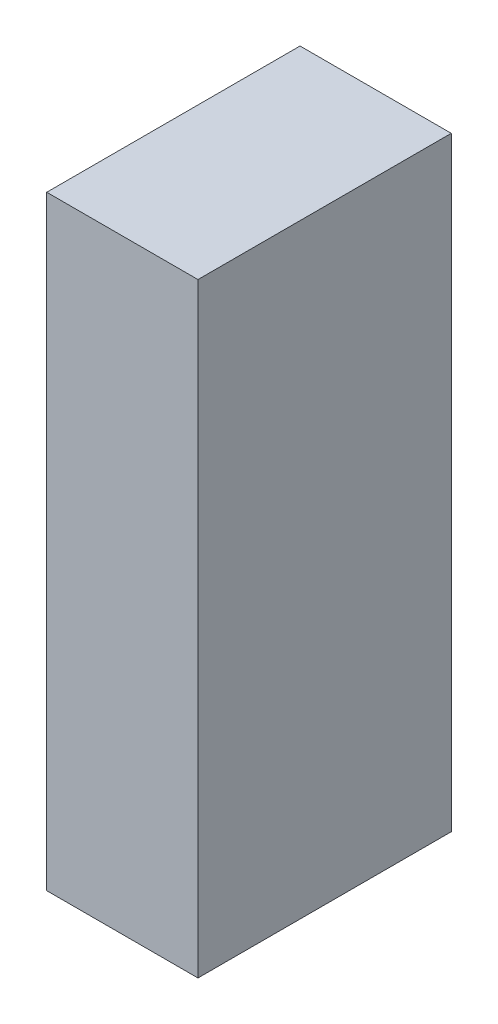
SolidWorks part; units mm, degrees
material "Polyester Resin"
ref_plane "Front Plane" through (0, 0, 0) normal (0, 0, 1) x (1, 0, 0)
ref_plane "Top Plane" through (0, 0, 0) normal (0, 1, 0) x (1, 0, 0)
ref_plane "Right Plane" through (0, 0, 0) normal (1, 0, 0) x (0, 0, -1)
sketch "Sketch1" plane through (0, 0, 0) normal (1, 0, 0) x (0, 0, -1)
  line L1 (-16.75, 40) -> (16.75, 40)
  line L2 (-16.75, 40) -> (-16.75, -40)
  line L3 (-16.75, -40) -> (16.75, -40)
  line L4 (16.75, 40) -> (16.75, -40)
  line L5 (0, -40) -> (0, 40) construction
  line L6 (-16.75, 0) -> (16.75, 0) construction
  point P0 (0, 0)
  dimension "D1" = 33.5
  dimension "D2" = 80
extrude "Boss-Extrude1" add sketch "Sketch1" along normal blind 20 contours L1 L4 L3 L2
